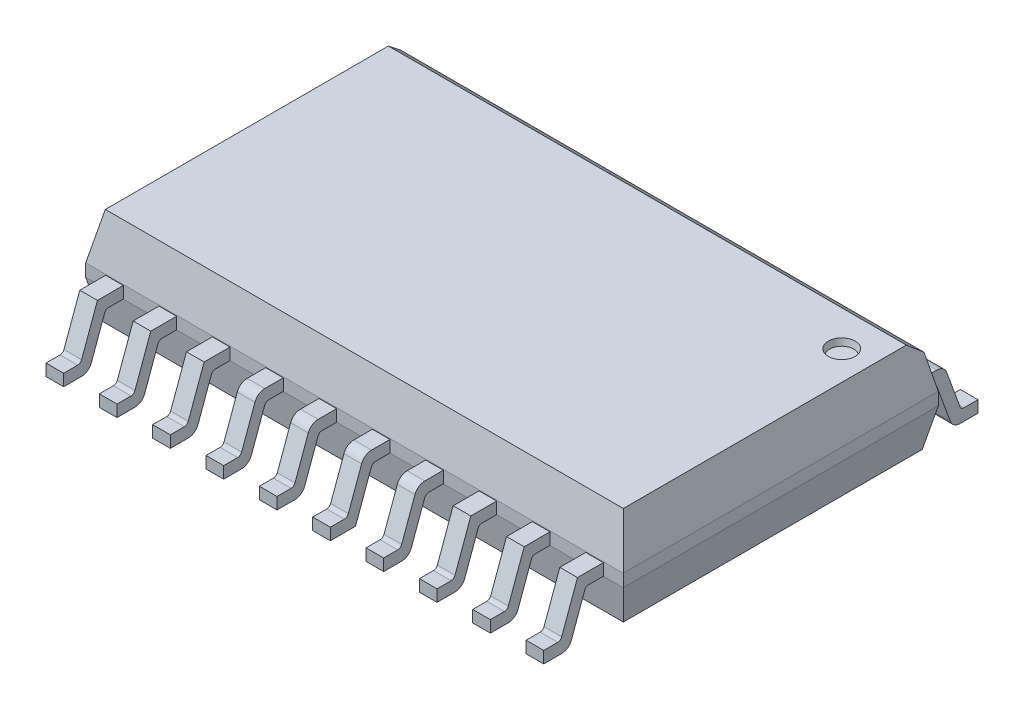
SolidWorks part; units mm, degrees
note: '?' marks a value the reader was unsure of.
ref_plane "Front Plane" through (0, 0, 0) normal (0, 0, 1) x (1, 0, 0)
ref_plane "Top Plane" through (0, 0, 0) normal (0, 1, 0) x (1, 0, 0)
ref_plane "Right Plane" through (0, 0, 0) normal (1, 0, 0) x (0, 0, -1)
ref_axis "Axis1" through (7.04, 0, 0) along (-1, 0, 0)?
sketch "Sketch1" plane through (0, 0, 0) normal (0, 1, 0) x (1, 0, 0)
  line L1 (-6.4, 3.75) -> (6.4, 3.75)
  line L2 (-6.4, 3.75) -> (-6.4, -3.75)
  line L3 (-6.4, -3.75) -> (6.4, -3.75)
  line L4 (6.4, 3.75) -> (6.4, -3.75)
  dimension "D1" = 12.8
  dimension "D2" = 7.5
  dimension "D3" = 6.4
  dimension "D4" = 3.75
extrude "Extrude1" add sketch "Sketch1" along normal blind 1.1 draft 12 and the other way blind 0.3
sketch "Sketch2" plane through (0, -0.3, 0) normal (0, -1, 0) x (1, 0, 0)
  line L4 (-6.4, 3.75) -> (-6.4, -3.75)
  line L5 (-6.4, -3.75) -> (6.4, -3.75)
  line L6 (6.4, -3.75) -> (6.4, 3.75)
  line L7 (6.4, 3.75) -> (-6.4, 3.75)
  line L8 (-6.4, 3.75) -> (-6.4, -3.75)
  line L9 (-6.4, -3.75) -> (6.4, -3.75)
  line L10 (6.4, -3.75) -> (6.4, 3.75)
  line L11 (6.4, 3.75) -> (-6.4, 3.75)
  dimension "D1" = 0
extrude "Extrude2" add sketch "Sketch2" along normal blind 0.9 draft 12
chamfer "Chamfer1" distance 0.3 angle 38.5 1 edges at (0, 1.1, -3.5162)
sketch "Sketch3" plane through (0, 1.1, 0) normal (0, 1, 0) x (-1, 0, 0)
  circle A0 centre (-5.473, -2.378) radius 0.3175
extrude "Cut-Extrude1" cut sketch "Sketch3" against normal blind 0.15 draft 12
sketch "Sketch4" plane through (0, 0, 0) normal (1, 0, 0) x (0, 0, -1)
  line L0 (0, -0.02) -> (0, -0.3)
  line L1 (-4.7661, -1.12) -> (-4.3657, -0.02)
  line L2 (-4.1696, -0.3) -> (4.1696, -0.3)
  line L3 (4.1696, -0.3) -> (4.57, -1.4)
  line L4 (-5.17, -1.12) -> (-4.7661, -1.12)
  line L5 (4.57, -1.4) -> (5.17, -1.4)
  line L6 (5.17, -1.4) -> (5.17, -1.12)
  line L7 (5.17, -1.12) -> (4.7661, -1.12)
  line L8 (4.7661, -1.12) -> (4.3657, -0.02)
  line L9 (4.3657, -0.02) -> (-4.3657, -0.02)
  line L10 (-5.17, -1.4) -> (-5.17, -1.12)
  line L11 (-4.57, -1.4) -> (-5.17, -1.4)
  line L12 (-4.1696, -0.3) -> (-4.57, -1.4)
  line L14 (-3.5587, -1.2) -> (3.5587, -1.2) construction
  line L15 (3.75, -0.3) -> (-3.75, -0.3) construction
  dimension "D1" = 0.28
  dimension "D2" = 0.28
  dimension "D3" = 0.28
  dimension "D4" = 0.6
  dimension "D5" = 10.34
  dimension "D6" = 110
  dimension "D7" = 0.2
extrude "Extrude3" add sketch "Sketch4" along normal blind 0.21 and the other way blind 0.21 from offset 0.635 contours L8 L9 L1 L4 L10 L11 L12 L2 L3 L5 L6 L7
pattern_linear "LPattern3" count 5 spacing 1.27 along (1, 0, 0) count 6 spacing 1.27 along (-1, 0, 0) of "Extrude3"
fillet "Fillet1" radius 0.1 40 edges at (1.905, -1.12, 4.7661) (0.635, -1.12, 4.7661) (-0.635, -1.12, 4.7661) (-1.905, -1.12, 4.7661) (1.905, -0.3, 4.1696) (0.635, -0.3, 4.1696) (-0.635, -0.3, 4.1696) (-1.905, -0.3, 4.1696) (1.905, -1.12, -4.7661) (0.635, -1.12, -4.7661) (-0.635, -1.12, -4.7661) (1.905, -0.3, -4.1696) (0.635, -0.3, -4.1696) (-0.635, -0.3, -4.1696) (-1.905, -0.3, -4.1696) (-1.905, -1.12, -4.7661) (5.715, -0.3, -4.1696) (4.445, -0.3, -4.1696) (3.175, -0.3, -4.1696) (-3.175, -0.3, -4.1696) (-4.445, -0.3, -4.1696) (-5.715, -0.3, -4.1696) (-5.715, -1.12, -4.7661) (-4.445, -1.12, -4.7661) (-3.175, -1.12, -4.7661) (5.715, -1.12, -4.7661) (4.445, -1.12, -4.7661) (3.175, -1.12, -4.7661) (-5.715, -1.12, 4.7661) (-4.445, -1.12, 4.7661) (-3.175, -1.12, 4.7661) (5.715, -1.12, 4.7661) (4.445, -1.12, 4.7661) (3.175, -1.12, 4.7661) (-5.715, -0.3, 4.1696) (-4.445, -0.3, 4.1696) (-3.175, -0.3, 4.1696) (5.715, -0.3, 4.1696) (4.445, -0.3, 4.1696) (3.175, -0.3, 4.1696)
fillet "Fillet2" radius 0.25 33 edges at (1.905, -1.4, 4.57) (1.905, -0.02, 4.3657) (-0.635, -0.02, 4.3657) (0.635, -0.02, 4.3657) (-0.635, -1.4, 4.57) (-1.905, -1.4, 4.57) (-1.905, -0.02, 4.3657) (1.905, -0.02, -4.3657) (0.635, -0.02, -4.3657) (-0.635, -0.02, -4.3657) (-1.905, -0.02, -4.3657) (1.905, -1.4, -4.57) (0.635, -1.4, -4.57) (-0.635, -1.4, -4.57) (-1.905, -1.4, -4.57) (-5.715, -1.4, 4.57) (-4.445, -1.4, 4.57) (-3.175, -1.4, 4.57) (5.715, -1.4, 4.57) (4.445, -1.4, 4.57) (3.175, -1.4, 4.57) (5.715, -1.4, -4.57) (4.445, -1.4, -4.57) (3.175, -1.4, -4.57) (-3.175, -1.4, -4.57) (-4.445, -1.4, -4.57) (-5.715, -1.4, -4.57) (5.715, -0.02, -4.3657) (4.445, -0.02, -4.3657) (3.175, -0.02, -4.3657) (-5.715, -0.02, -4.3657) (-4.445, -0.02, -4.3657) (-3.175, -0.02, -4.3657)
ref_plane "Plane1" through (0, -1.4, 0) normal (0, 1, 0) x (-1, 0, 0)
sketch "Component_Outline" plane through (0, -1.4, 0) normal (0, 1, 0) x (-1, 0, 0)
  line L0 (6.4, -3.75) -> (5.925, -3.75)
  line L1 (-1.695, -5.17) -> (-2.115, -5.17)
  line L2 (5.505, -5.17) -> (5.505, -3.75)
  line L3 (5.505, -3.75) -> (4.655, -3.75)
  line L4 (4.655, -5.17) -> (4.655, -3.75)
  line L5 (-4.235, -5.17) -> (-4.655, -5.17)
  line L6 (4.235, -5.17) -> (4.235, -3.75)
  line L7 (4.235, -3.75) -> (3.385, -3.75)
  line L8 (3.385, -5.17) -> (3.385, -3.75)
  line L9 (-5.505, -5.17) -> (-5.925, -5.17)
  line L10 (2.965, -5.17) -> (2.965, -3.75)
  line L11 (2.965, -3.75) -> (2.115, -3.75)
  line L12 (2.115, -5.17) -> (2.115, -3.75)
  line L13 (-6.4, 0) -> (6.4, 0) construction
  line L14 (1.695, -5.17) -> (1.695, -3.75)
  line L15 (1.695, -3.75) -> (0.845, -3.75)
  line L16 (0.845, -5.17) -> (0.845, -3.75)
  line L17 (-2.965, 5.17) -> (-3.385, 5.17)
  line L18 (0.425, -5.17) -> (0.425, -3.75)
  line L19 (0.425, -3.75) -> (-0.425, -3.75)
  line L20 (-0.425, -5.17) -> (-0.425, -3.75)
  line L21 (-6.4, -3.75) -> (-6.4, 3.75)
  line L22 (-0.845, -5.17) -> (-0.845, -3.75)
  line L23 (-0.845, -3.75) -> (-1.695, -3.75)
  line L24 (-1.695, -5.17) -> (-1.695, -3.75)
  line L26 (-2.115, -5.17) -> (-2.115, -3.75)
  line L27 (-2.115, -3.75) -> (-2.965, -3.75)
  line L28 (-2.965, -5.17) -> (-2.965, -3.75)
  line L30 (-3.385, -5.17) -> (-3.385, -3.75)
  line L31 (-3.385, -3.75) -> (-4.235, -3.75)
  line L32 (-4.235, -5.17) -> (-4.235, -3.75)
  line L34 (-4.655, -5.17) -> (-4.655, -3.75)
  line L35 (-4.655, -3.75) -> (-5.505, -3.75)
  line L36 (-5.505, -5.17) -> (-5.505, -3.75)
  line L37 (5.925, -3.75) -> (5.925, -5.17)
  line L38 (5.925, -5.17) -> (5.505, -5.17)
  line L39 (-5.925, -5.17) -> (-5.925, -3.75)
  line L40 (-5.925, -3.75) -> (-6.4, -3.75)
  line L41 (4.655, -5.17) -> (4.235, -5.17)
  line L42 (3.385, -5.17) -> (2.965, -5.17)
  line L43 (2.115, -5.17) -> (1.695, -5.17)
  line L44 (0.845, -5.17) -> (0.425, -5.17)
  line L45 (-0.425, -5.17) -> (-0.845, -5.17)
  line L46 (-2.965, -5.17) -> (-3.385, -5.17)
  line L47 (-6.4, 3.75) -> (-6.4, -3.75) construction
  line L48 (6.4, -3.75) -> (6.4, 3.75) construction
  line L50 (-0.425, 5.17) -> (-0.845, 5.17)
  line L51 (0.845, 5.17) -> (0.425, 5.17)
  line L52 (2.115, 5.17) -> (1.695, 5.17)
  line L53 (3.385, 5.17) -> (2.965, 5.17)
  line L54 (4.655, 5.17) -> (4.235, 5.17)
  line L55 (-5.925, 3.75) -> (-6.4, 3.75)
  line L56 (-5.925, 5.17) -> (-5.925, 3.75)
  line L57 (5.925, 5.17) -> (5.505, 5.17)
  line L58 (5.925, 3.75) -> (5.925, 5.17)
  line L59 (-5.505, 5.17) -> (-5.505, 3.75)
  line L60 (-4.655, 3.75) -> (-5.505, 3.75)
  line L61 (-4.655, 5.17) -> (-4.655, 3.75)
  line L62 (-4.235, 5.17) -> (-4.235, 3.75)
  line L63 (-3.385, 3.75) -> (-4.235, 3.75)
  line L64 (-3.385, 5.17) -> (-3.385, 3.75)
  line L65 (-2.965, 5.17) -> (-2.965, 3.75)
  line L66 (-2.115, 3.75) -> (-2.965, 3.75)
  line L67 (-2.115, 5.17) -> (-2.115, 3.75)
  line L68 (-1.695, 5.17) -> (-1.695, 3.75)
  line L69 (-0.845, 3.75) -> (-1.695, 3.75)
  line L70 (-0.845, 5.17) -> (-0.845, 3.75)
  line L71 (-0.425, 5.17) -> (-0.425, 3.75)
  line L72 (0.425, 3.75) -> (-0.425, 3.75)
  line L73 (0.425, 5.17) -> (0.425, 3.75)
  line L74 (0.845, 5.17) -> (0.845, 3.75)
  line L75 (1.695, 3.75) -> (0.845, 3.75)
  line L76 (1.695, 5.17) -> (1.695, 3.75)
  line L77 (2.115, 5.17) -> (2.115, 3.75)
  line L78 (2.965, 3.75) -> (2.115, 3.75)
  line L79 (2.965, 5.17) -> (2.965, 3.75)
  line L80 (-5.505, 5.17) -> (-5.925, 5.17)
  line L81 (3.385, 5.17) -> (3.385, 3.75)
  line L82 (4.235, 3.75) -> (3.385, 3.75)
  line L83 (4.235, 5.17) -> (4.235, 3.75)
  line L84 (-4.235, 5.17) -> (-4.655, 5.17)
  line L85 (4.655, 5.17) -> (4.655, 3.75)
  line L86 (5.505, 3.75) -> (4.655, 3.75)
  line L87 (5.505, 5.17) -> (5.505, 3.75)
  line L88 (-1.695, 5.17) -> (-2.115, 5.17)
  line L89 (6.4, 3.75) -> (5.925, 3.75)
  line L90 (6.4, -3.75) -> (6.4, 3.75)
